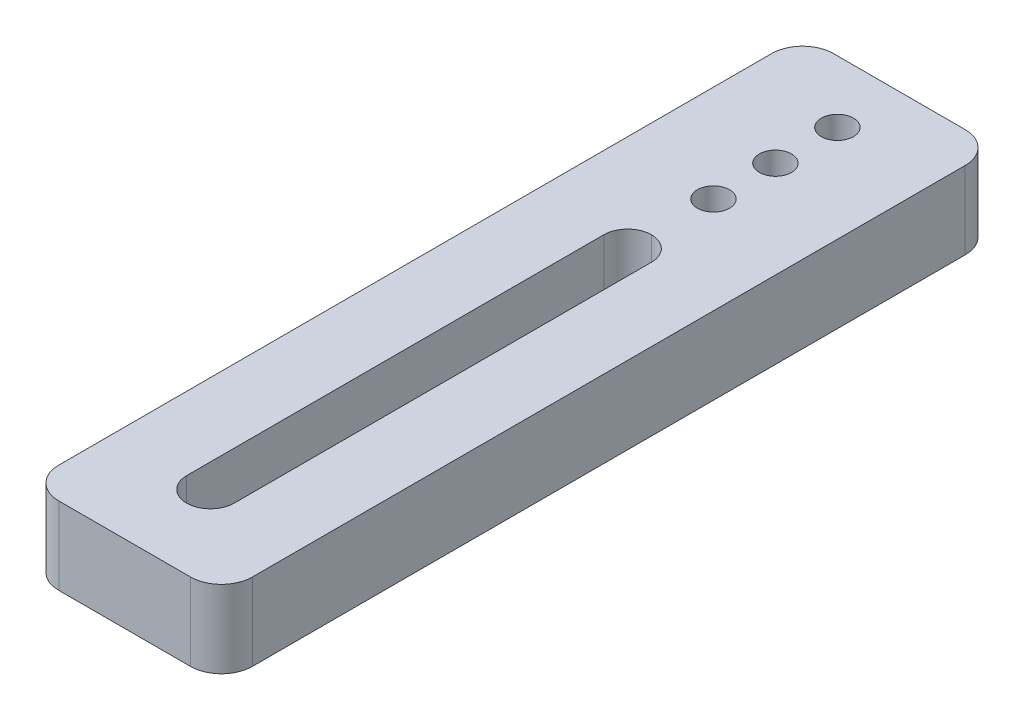
SolidWorks part; units mm, degrees
ref_plane "Front Plane" through (0, 0, 0) normal (0, 0, 1) x (1, 0, 0)
ref_plane "Top Plane" through (0, 0, 0) normal (0, 1, 0) x (1, 0, 0)
ref_plane "Right Plane" through (0, 0, 0) normal (1, 0, 0) x (0, 0, -1)
sketch "Sketch1" plane through (0, 0, 0) normal (0, 1, 0) x (1, 0, 0)
  line L1 (-12.5, -50) -> (12.5, -50)
  line L2 (-12.5, -50) -> (-12.5, 50)
  line L3 (-12.5, 50) -> (12.5, 50)
  line L4 (12.5, -50) -> (12.5, 50)
  line L5 (0, 50) -> (0, -50) construction
  line L6 (-12.5, 0) -> (12.5, 0) construction
  point P0 (0, 0)
  dimension "D1" = 25
  dimension "D2" = 100
extrude "Boss-Extrude1" add sketch "Sketch1" along normal blind 10
sketch "Sketch3" plane through (0, 10, 0) normal (0, 1, 0) x (1, 0, 0)
  line L0 (0, -42) -> (0, 18)
  line L1 (-12.5, -50) -> (12.5, -50) construction
  point P5 (0, -50)
  dimension "D1" = 8
  dimension "D2" = 60
extrude "Cut-Extrude-Thin2" cut sketch "Sketch3" against normal blind 10 and the other way through all thin thin type mid plane wall 6.15
fillet "Fillet2" radius 3.075 4 edges at (3.075, 5, -18) (-3.075, 5, -18) (3.075, 5, 42) (-3.075, 5, 42)
fillet "Fillet3" radius 4 4 edges at (-12.5, 5, 50) (12.5, 5, 50) (12.5, 5, -50) (-12.5, 5, -50)
sketch "Sketch4" plane through (0, 10, 0) normal (0, 1, 0) x (1, 0, 0)
  line L0 (8.5, 50) -> (-8.5, 50) construction
  circle A0 centre (0, 42) radius 2.075
  dimension "D1" = 4.15
  dimension "D2" = 8
extrude "Cut-Extrude1" cut sketch "Sketch4" against normal through all
pattern_linear "LPattern1" count 3 spacing 8 along (0, 0, 1) of "Cut-Extrude1"
